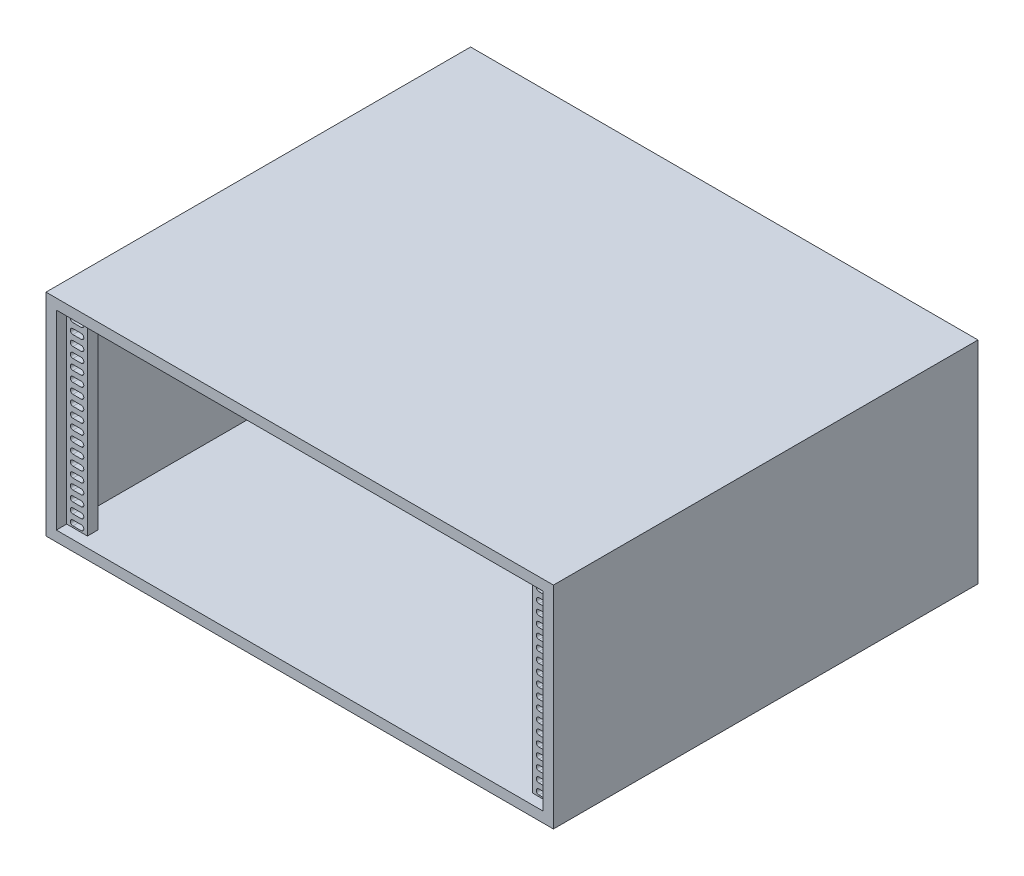
SolidWorks part; units mm, degrees
material "AISI 1015 Steel, Cold Drawn (SS)"
ref_plane "Front Plane" through (0, 0, 0) normal (0, 0, 1) x (1, 0, 0)
ref_plane "Top Plane" through (0, 0, 0) normal (0, 1, 0) x (1, 0, 0)
ref_plane "Right Plane" through (0, 0, 0) normal (1, 0, 0) x (0, 0, -1)
sketch "Sketch1" plane through (0, 0, 0) normal (0, 0, 1) x (1, 0, 0)
  line L0 (235, 92) -> (-235, 92)
  line L1 (245, -102) -> (-245, -102)
  line L2 (245, -102) -> (245, 102)
  line L3 (245, 102) -> (-245, 102)
  line L4 (-245, -102) -> (-245, 102)
  line L5 (245, -102) -> (-245, 102) construction
  line L6 (245, 102) -> (-245, -102) construction
  line L7 (-235, -92) -> (-235, 92)
  line L8 (235, -92) -> (-235, -92)
  line L9 (235, -92) -> (235, 92)
  point P0 (0, 0)
  dimension "D1" = 490
  dimension "D2" = 204
  dimension "D3" = 10
extrude "Boss-Extrude1" add sketch "Sketch1" against normal blind 410
sketch "Sketch2" plane through (0, 0, 0) normal (0, 0, 1) x (1, 0, 0)
  line L0 (235, 92) -> (-235, 92) construction
  line L1 (-235, 92) -> (-235, -92) construction
  line L2 (-235, -92) -> (235, -92) construction
  line L3 (-215, 92) -> (-235, 92)
  line L4 (-235, 92) -> (-235, -92)
  line L5 (-235, -92) -> (-215, -92)
  line L6 (-215, 92) -> (-215, -92)
  dimension "D1" = 215
extrude "Boss-Extrude2" add sketch "Sketch2" along normal blind 10 from offset 20 offset against normal yes
sketch "Sketch3" plane through (0, 0, -10) normal (0, 0, 1) x (1, 0, 0)
  line L0 (-215, 92) -> (-235, 92) construction
  line L1 (-215, 92) -> (-235, 92) construction
  line L2 (-225, 92) -> (-225, 25.528) construction
  line L3 (-229, 82) -> (-221, 82) construction
  line L4 (-229, 84.5) -> (-221, 84.5)
  line L5 (-229, 79.5) -> (-221, 79.5)
  arc A0 (-229, 84.5) -> (-229, 79.5) centre (-229, 82) ccw
  arc A1 (-221, 79.5) -> (-221, 84.5) centre (-221, 82) ccw
  point P6 (-225, 82)
  dimension "D2" = 2.5
  dimension "D1" = 8
  dimension "D3" = 10
extrude "Cut-Extrude1" cut sketch "Sketch3" against normal up to next
pattern_linear "LPattern1" count 18 spacing 10 along (0, -1, 0) of "Cut-Extrude1"
mirror "Mirror1" about plane through (0, 0, 0) normal (1, 0, 0) of "LPattern1", "Cut-Extrude1", "Boss-Extrude2"
